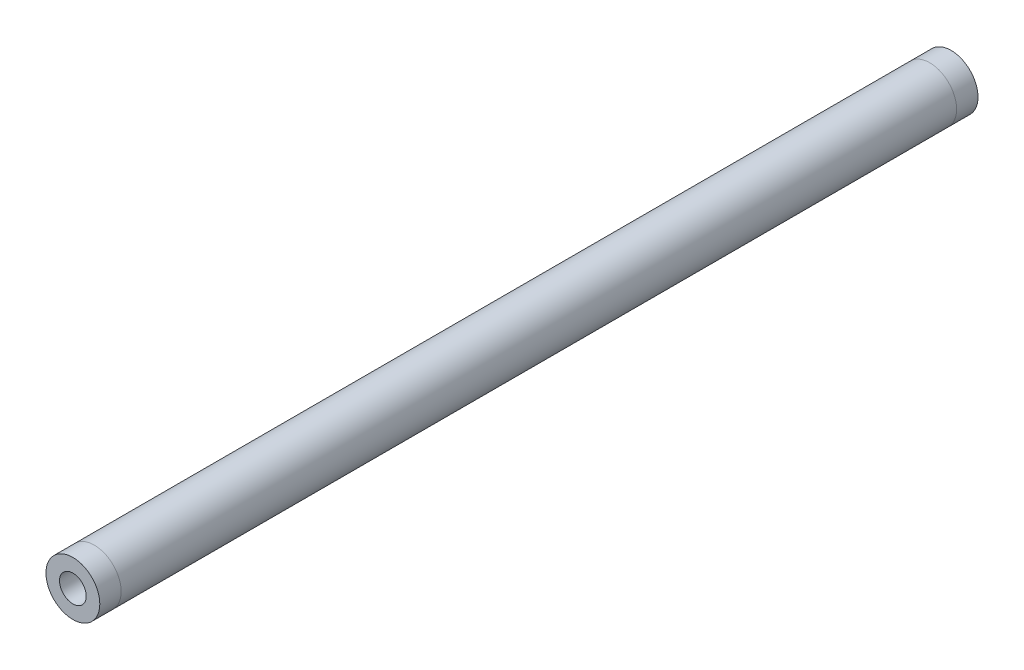
SolidWorks part; units mm, degrees
ref_plane "Front Plane" through (0, 0, 0) normal (0, 0, 1) x (1, 0, 0)
ref_plane "Top Plane" through (0, 0, 0) normal (0, 1, 0) x (1, 0, 0)
ref_plane "Right Plane" through (0, 0, 0) normal (1, 0, 0) x (0, 0, -1)
sketch "Axis" plane through (0, 0, 0) normal (1, 0, 0) x (0, 0, -1)
  line L0 (0, 0) -> (260.8962, 0) construction
  line L1 (260.8962, 0) -> (254.5462, 0)
  line L2 (260.8962, 0) -> (295.8212, 0) construction
  line L3 (0, 0) -> (-34.925, 0) construction
  point P4 (0, 0)
  point P5 (260.8962, 0)
  point P6 (254.5462, 0)
  dimension "D1" = 6.35
  dimension "D2" = 34.925
  dimension "D3" = 34.925
sketch "Sketch1" plane through (0, 0, 0) normal (0, 0, 1) x (1, 0, 0)
  circle A0 centre (0, 0) radius 8.001
  circle A1 centre (0, 0) radius 6.477
  circle A2 centre (0, 0) radius 3.9688
  dimension "D1" = 16.002
  dimension "D2" = 1.524
  dimension "D3" = 7.9375
extrude "Threaded insert 1-1" add sketch "Sketch1" against normal blind 6.35 contours A0 A1 | A1 A2 region at (-7.7747, 0, 0) region at (-6.2938, 0, 0)
extrude "Threaded insert 1-2" add sketch "Sketch1<3>" against normal blind 9.525 from surface contours A1 A2 region at (-6.2938, 0, 0) starting at face at (8.001, 0, -6.35)
sketch "Sketch1<3>" plane through (0, 0, 0) normal (0, 0, 1) x (1, 0, 0) same geometry as "Sketch1"
extrude "Tube extrude" add sketch "Sketch1<4>" against normal up to vertex (254.5462 mm away) from surface separate body contours A0 A1 region at (-7.7747, 0, 0) up to point (0, 0, -254.5462) starting at face at (6.477, 0, -6.35)
sketch "Sketch1<4>" plane through (0, 0, 0) normal (0, 0, 1) x (1, 0, 0) same geometry as "Sketch1"
extrude "Threaded insert 2-1" add sketch "Sketch1<6>" along normal blind 9.525 from surface separate body contours A1 A2 region at (-6.2938, 0, 0) starting at face at (6.477, 0, -254.5462)
sketch "Sketch1<6>" plane through (0, 0, 0) normal (0, 0, 1) x (1, 0, 0) same geometry as "Sketch1"
extrude "Threaded insert 2-2" add sketch "Sketch1<9>" against normal blind 6.35 from surface separate body contours A1 A2 | A0 A1 region at (-7.7747, 0, 0) region at (-6.2938, 0, 0) starting at face at (6.477, 0, -254.5462)
sketch "Sketch1<9>" plane through (0, 0, 0) normal (0, 0, 1) x (1, 0, 0) same geometry as "Sketch1"
combine bodies "Combine1" operation type add bodies to combine 106 104
equation "\"Threaded insert outer thickness\"= .25"
equation "\"D1@Threaded insert 1-1\"=\"Threaded insert outer thickness\""
equation "\"D1@Threaded insert 2-2\"=\"Threaded insert outer thickness\""
equation "\"D1@Axis\" = \"Threaded insert outer thickness\""
